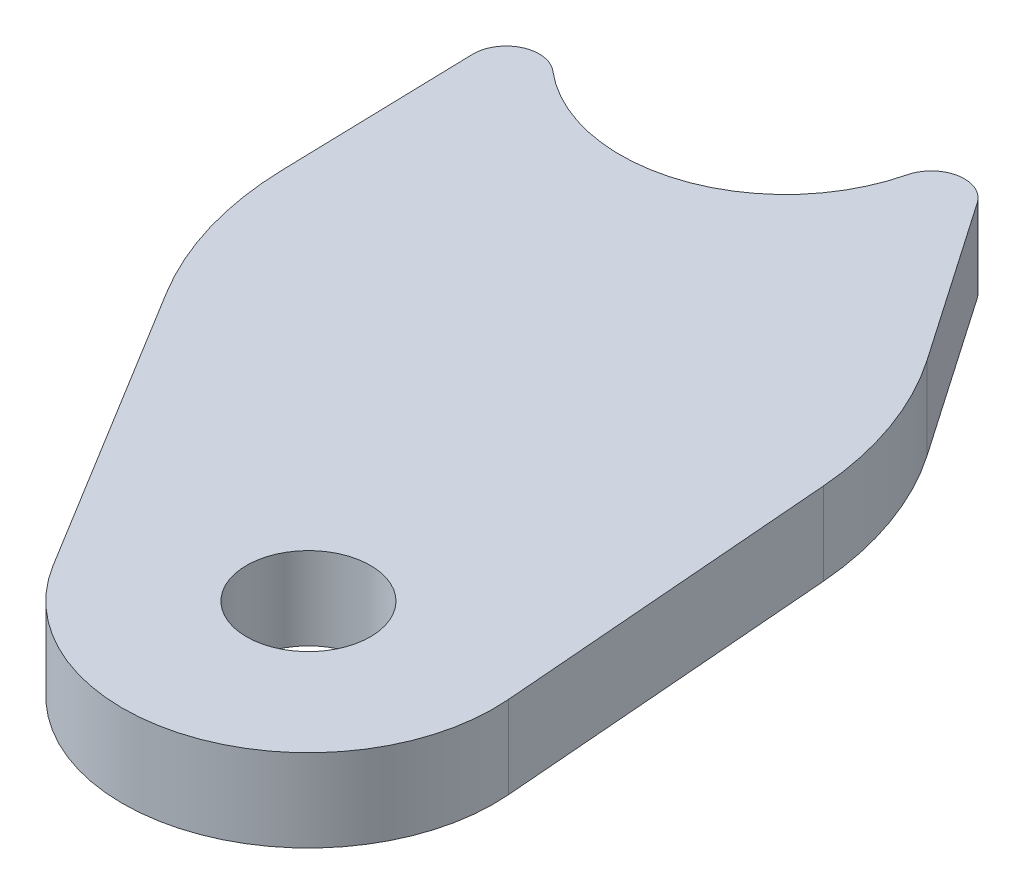
SolidWorks part; units mm, degrees
ref_plane "Front Plane" through (0, 0, 0) normal (0, 0, 1) x (1, 0, 0)
ref_plane "Top Plane" through (0, 0, 0) normal (0, 1, 0) x (1, 0, 0)
ref_plane "Right Plane" through (0, 0, 0) normal (1, 0, 0) x (0, 0, -1)
sketch3d "reference sketch"
  line L1 (0, -6.35, -54.4099) -> (183.4, -41.6461, 508.7764) construction
  line L2 (0, 0, 0) -> (413.3685, 0, 0) construction
  line L3 (0, 0, -54.4099) -> (0, 0, 0) construction
  line L5 (25.4, -177.8, -54.4099) -> (533.4, -177.8, -54.4099) construction
  line L7 (549.7633, -56.819, -15.8279) -> (0, -177.8, -54.4099) construction
  circle A0 centre (0, 0, -54.4099) radius 12.7 construction
  point P4 (0, -12.7, -54.4099)
  point P9 (25.4, -152.4, 25.4)
sketch "Sketch13" plane through (0, 0, 0) normal (0, 1, 0) x (1, 0, 0)
  line L0 (10.4572, 61.6166) -> (29.3113, 34.2588)
  line L1 (-12.6956, 54.077) -> (10.4572, 61.6166)
  line L2 (29.3113, 34.2588) -> (31.9604, 1.1392)
  line L3 (0, 54.4099) -> (183.4, -508.7764) construction
  line L4 (0, 54.4099) -> (17.7184, 0) construction
  line L5 (-11.8247, 20.863) -> (5.5366, -7.4657)
  line L6 (-12.6956, 54.077) -> (-11.8247, 20.863)
  line L7 (10.4572, 61.6166) -> (31.9604, 1.1392) construction
  line L8 (0, 0) -> (413.3685, 0) construction
  arc A0 (31.9604, 1.1392) -> (5.5366, -7.4657) centre (17.7184, 0) cw
  circle A1 centre (0, 54.4099) radius 12.7 construction
  circle A2 centre (17.7184, 0) radius 4.7625
  arc A3 (-12.6956, 54.077) -> (10.4572, 61.6166) centre (0, 54.4099) ccw construction
  point P6 (0, 0)
  point P10 (0, 0)
  point P11 (19.0064, 0.3695)
  point P15 (0, 0)
  point P16 (0, 0)
  dimension "D2" = 9.525
  dimension "D1" = 9.525
  dimension "D3" = 15
extrude "Boss-Extrude1" add sketch "Sketch13" along normal blind 6.35
sketch "Sketch14" plane through (0, 0, 0) normal (0, 1, 0) x (1, 0, 0)
  circle A0 centre (0, 54.4099) radius 12.7 construction
  circle A1 centre (0, 54.4099) radius 12.7
extrude "Cut-Extrude1" cut sketch "Sketch14" against normal through all both and the other way through all
fillet "Fillet1" radius 2.54 2 edges at (10.4572, 3.175, -61.6166) (-12.6956, 3.175, -54.077)
fillet "Fillet2" radius 25.4 2 edges at (29.3113, 3.175, -34.2588) (-11.8247, 3.175, -20.863)
equation "\"D1@Sketch13\"=\"D2@Sketch13\"*1"
